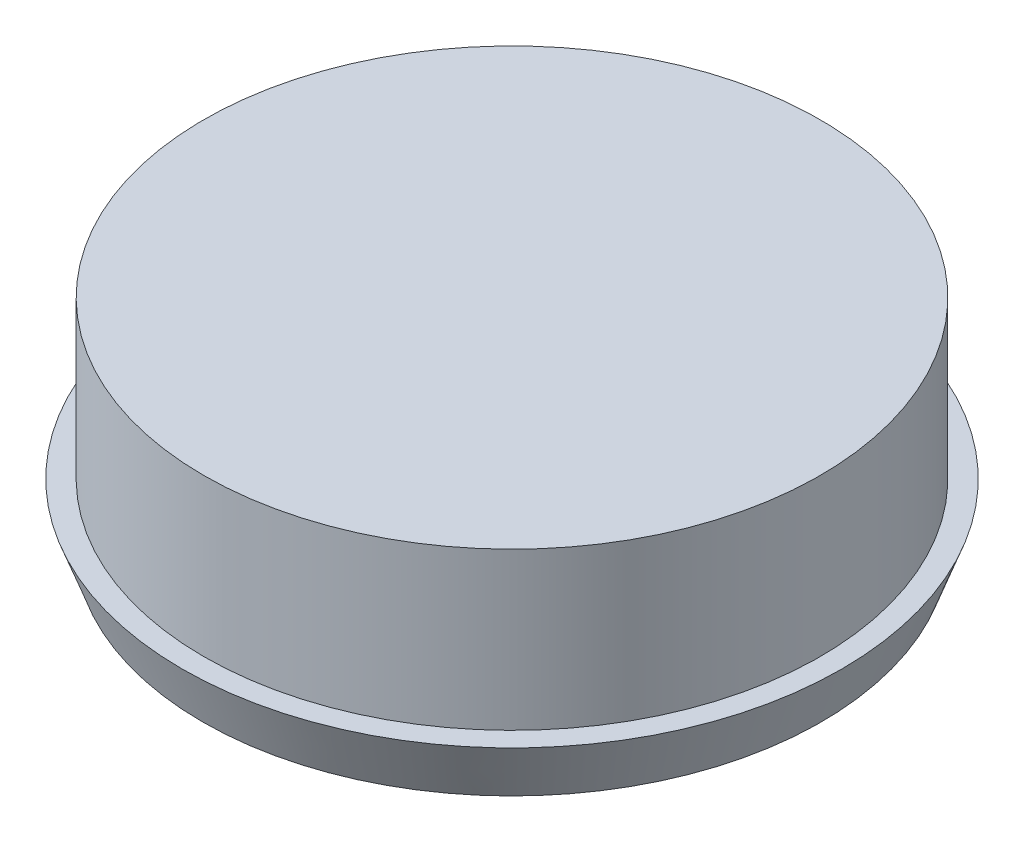
SolidWorks part; units mm, degrees
ref_plane "Front Plane" through (0, 0, 0) normal (0, 0, 1) x (1, 0, 0)
ref_plane "Top Plane" through (0, 0, 0) normal (0, 1, 0) x (1, 0, 0)
ref_plane "Right Plane" through (0, 0, 0) normal (1, 0, 0) x (0, 0, -1)
sketch "Sketch1" plane through (0, 0, 0) normal (0, 1, 0) x (1, 0, 0)
  circle A0 centre (0, 0) radius 29.5
  dimension "D1" = 59
extrude "Boss-Extrude1" add sketch "Sketch1" along normal blind 5
sketch "Sketch2" plane through (0, 5, 0) normal (0, 1, 0) x (1, 0, 0)
  circle A0 centre (0, 0) radius 27.5
  dimension "D1" = 55
extrude "Boss-Extrude2" add sketch "Sketch2" along normal blind 14
chamfer "Chamfer1" distance 1.9 angle 70 1 edges at (0, 0, 29.5) first distance on face at (0, 0, 29.5)
sketch "Sketch3" plane through (0, 0, 0) normal (0, -1, 0) x (1, 0, 0)
  line L0 (0, 0) -> (0, 12.5) construction
  circle A0 centre (0, 12.5) radius 1.5
  circle A1 centre (12.5, 0) radius 1.5
  circle A2 centre (0, -12.5) radius 1.5
  circle A3 centre (-12.5, 0) radius 1.5
  point P4 (-18.1665, -5.8691)
  point P5 (0, 0)
  point P13 (0, 0)
  dimension "D2" = 3
  dimension "D1" = 12.5
  dimension "D3" = 4
extrude "Cut-Extrude1" cut sketch "Sketch3" against normal blind 3.5
sketch "Sketch4" plane through (0, 0, 0) normal (0, -1, 0) x (1, 0, 0)
  circle A0 centre (0, 0) radius 3
  dimension "D1" = 6
extrude "Boss-Extrude3" add sketch "Sketch4" along normal blind 2.7
chamfer "Chamfer2" distance 0.2 angle 45 1 edges at (0, -2.7, -3)
